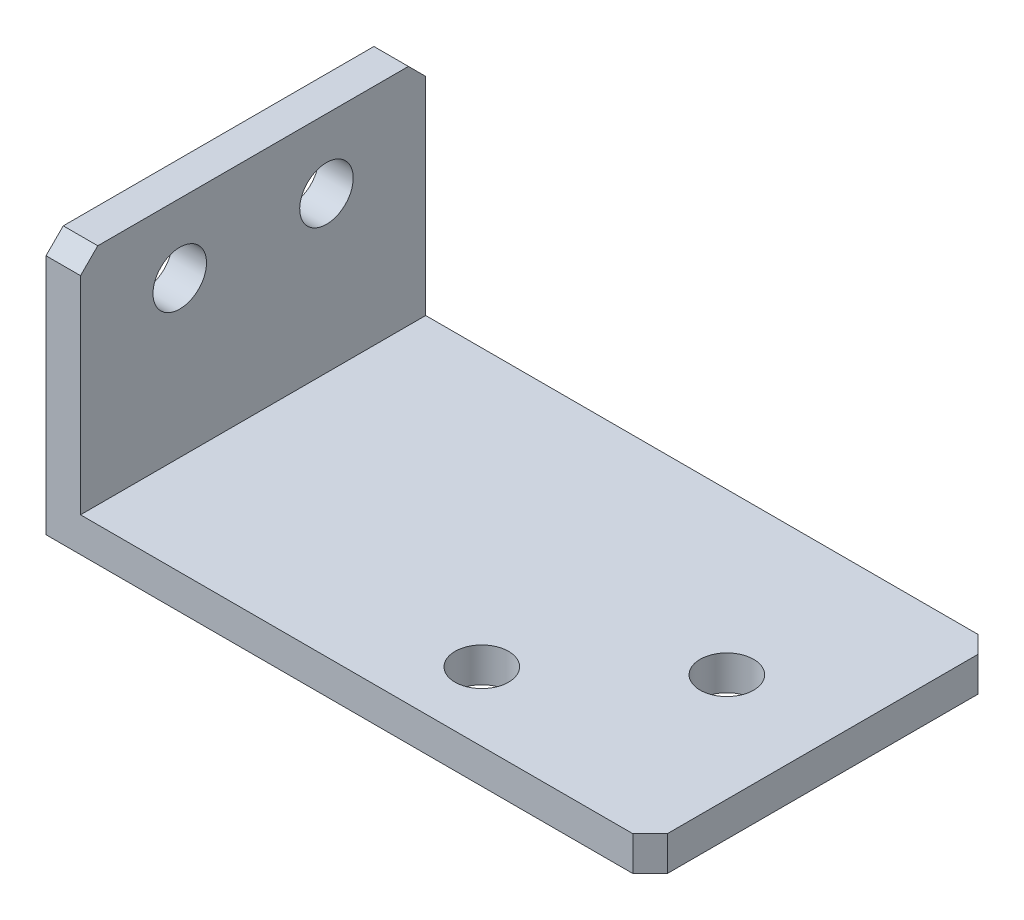
SolidWorks part; units mm, degrees
material "6063-T5"
ref_plane "Спереди" through (0, 0, 0) normal (0, 0, 1) x (1, 0, 0)
ref_plane "Сверху" through (0, 0, 0) normal (0, 1, 0) x (1, 0, 0)
ref_plane "Справа" through (0, 0, 0) normal (1, 0, 0) x (0, 0, -1)
sketch "Sketch1" plane through (0, 0, 0) normal (0, 0, 1) x (1, 0, 0)
  line L0 (0, 0) -> (35, 0)
  line L1 (35, 0) -> (35, 2)
  line L2 (35, 2) -> (2, 2)
  line L3 (2, 2) -> (2, 15)
  line L4 (2, 15) -> (0, 15)
  line L5 (0, 15) -> (0, 0)
  dimension "D1" = 35
  dimension "D2" = 15
  dimension "D3" = 2
  dimension "D4" = 2
extrude "Base" add sketch "Sketch1" along normal blind 20
sketch "Sketch2" plane through (0, 0, 0) normal (-1, 0, 0) x (0, 0, 1)
  line L2 (20, 0) -> (0, 0) construction
  line L3 (10, 0) -> (10, 14.2922) construction
  circle A0 centre (14.25, 11) radius 1.55
  circle A1 centre (5.75, 11) radius 1.55
  dimension "D5" = 3.1
  dimension "D1" = 8.5
  dimension "D3" = 11
extrude "CarriageSide" cut sketch "Sketch2" against normal up to surface (2 mm away) up to face at (2, 8.5, 10)
sketch "Sketch5" plane through (0, 2, 0) normal (0, 1, 0) x (1, 0, 0)
  line L0 (0, -20) -> (0, 0) construction
  line L2 (35, -20) -> (2, -20) construction
  circle A0 centre (21.25, -16) radius 1.55
  circle A1 centre (28.75, -9.3) radius 1.55
  dimension "D3" = 3.1
  dimension "D1" = 4
  dimension "D2" = 6.7
  dimension "D4" = 7.5
  dimension "D5" = 21.25
extrude "CableChainSide" cut sketch "Sketch5" against normal through all
chamfer "Chamfer1" distance 1 angle 45 4 edges at (35, 1, 0) (1, 15, 0) (1, 15, 20) (35, 1, 20)
